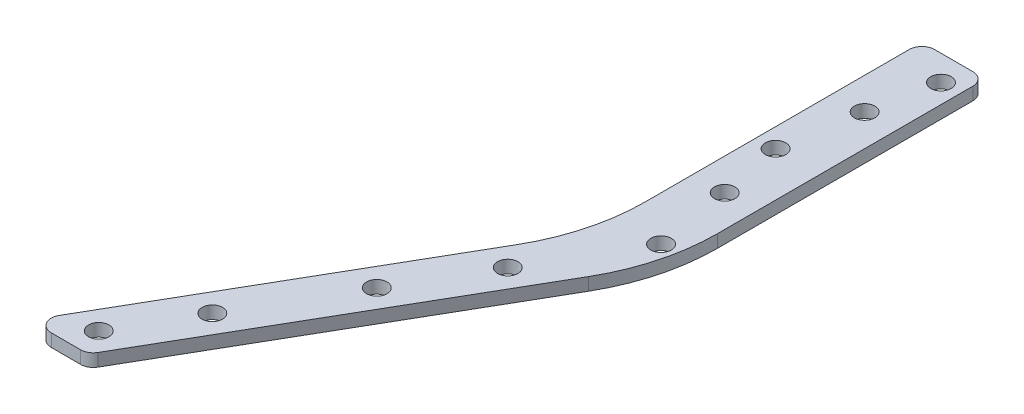
SolidWorks part; units mm, degrees
material "6061-T6 (SS)"
ref_plane "Front" through (0, 0, 0) normal (0, 0, 1) x (1, 0, 0)
ref_plane "Top" through (0, 0, 0) normal (0, 1, 0) x (1, 0, 0)
ref_plane "Right" through (0, 0, 0) normal (1, 0, 0) x (0, 0, -1)
sketch "Sketch1" plane through (0, 0, 0) normal (0, 1, 0) x (1, 0, 0)
  line L0 (0, -82.55) -> (-51.3264, -171.45)
  line L1 (0, 0) -> (15.875, 0)
  line L2 (0, 0) -> (0, -82.55)
  line L4 (15.875, 0) -> (15.875, -80.4537)
  line L7 (-51.3264, -171.45) -> (-36.6617, -171.45)
  line L8 (-36.6617, -171.45) -> (15.875, -80.4537)
  dimension "D1" = 15.875
  dimension "D2" = 82.55
  dimension "D3" = 12.7
  dimension "D4" = 171.45
  dimension "D5" = 150
base flange "Base-Flange1" sketch "Sketch1" thickness 3.175 reverse thickness direction no parameters "D1"=3.175
sketch "Sketch6" plane through (0, 0, 0) normal (0, 1, 0) x (1, 0, 0)
  line L1 (11.1125, -6.35) -> (4.7625, -41.275) construction
  line L3 (4.7625, -41.275) -> (11.1125, -76.2) construction
  line L4 (15.875, -80.4537) -> (15.875, 0) construction
  line L5 (0, 0) -> (0, -82.55) construction
  line L6 (15.875, 0) -> (0, 0) construction
  line L7 (6.1452, -84.6063) -> (-43.9941, -171.45) construction
  line L8 (0, -82.55) -> (-51.3264, -171.45) construction
  line L9 (-51.3264, -171.45) -> (-36.6617, -171.45) construction
  circle A4 centre (-40.3279, -165.1) radius 2.5527
  circle A5 centre (-14.9279, -121.1059) radius 2.5527
  circle A6 centre (11.1125, -6.35) radius 2.5527
  circle A7 centre (4.7625, -41.275) radius 2.5527
  circle A8 centre (11.1125, -76.2) radius 2.5527
  dimension "D1" = 5.1054
  dimension "D2" = 69.85
  dimension "D3" = 4.7625
  dimension "D4" = 4.7625
  dimension "D5" = 6.35
  dimension "D7" = 5.1054
  dimension "D8" = 6.35
  dimension "D9" = 50.8
  dimension "D6" = 6.35
extrude "Cut-Extrude1" cut sketch "Sketch6" against normal through all normal cut yes
fillet "Fillet1" radius 3.175 4 edges at (0, -1.5875, 0) (15.875, -1.5875, 0) (-51.3264, -1.5875, 171.45) (-36.6617, -1.5875, 171.45)
fillet "Fillet2" radius 50.8 2 edges at (0, -1.5875, 82.55) (15.875, -1.5875, 80.4537)
sketch "Sketch9" plane through (0, 0, 0) normal (0, 1, 0) x (1, 0, 0)
  line L0 (7.9375, 0) -> (7.9375, -105.5093) construction
  line L1 (12.7, 0) -> (3.175, 0) construction
  line L2 (-45.8272, -174.625) -> (6.0364, -84.7946) construction
  line L4 (-51.3264, -171.45) -> (-40.3279, -177.8) construction
  line L6 (-6.8059, -94.3382) -> (-48.5768, -166.6875) construction
  line L7 (-45.8272, -171.45) -> (-38.4948, -171.45) construction
  line L8 (-35.7452, -169.8625) -> (9.0691, -92.2419) construction
  point P0 (7.9375, -22.225)
  point P2 (7.9375, -57.15)
  point P4 (-2.9647, -100.385)
  point P6 (-29.9522, -147.1287)
  dimension "D1" = 22.225
  dimension "D2" = 34.925
  dimension "D3" = 31.75
  dimension "D4" = 85.725
hole_wizard "#10 Clearance Hole1" positions "Sketch9" profile "Sketch8" hole size "#10" standard "ANSI Inch" end condition through all
sketch "Sketch8" plane through (7.9375, 0, 22.225) normal (1, 0, 0) x (0, 0, 1)
  line L0 (0, 0) -> (0, 3.175)
  line L1 (0, 3.175) -> (2.5527, 3.175)
  line L2 (2.5527, 3.175) -> (2.5527, 0)
  line L5 (2.5527, 0) -> (0, 0)
  line L11 (0, -6.35) -> (0, 107.95) construction
  dimension "Thru Hole Dia." = 5.1054
  dimension "Thru Hole Depth" = 3.175
sketch "Bend-Lines1" [suppressed] plane through (0, 0, 0) normal (0, 1, 0) x (1, 0, 0)
sketch "Bounding-Box1" [suppressed] plane through (0, 0, 0) normal (0, 1, 0) x (1, 0, 0)
sheet metal parameters "Sheet-Metal8" thickness 3.175 parameters "D1"=3.175
flat pattern "Flat-Pattern8" [suppressed]
sketch "Bend-Lines2" plane through (0, 0, 0) normal (0, 1, 0) x (1, 0, 0)
sketch "Bounding-Box2" [suppressed] plane through (0, 0, 0) normal (0, 1, 0) x (1, 0, 0)
sheet metal parameters "Sheet-Metal9" thickness 3.175 parameters "D1"=3.175
flat pattern "Flat-Pattern8"
sketch "Bend-Lines2" plane through (0, 0, 0) normal (0, 1, 0) x (1, 0, 0)
sketch "Bounding-Box2" [suppressed] plane through (0, 0, 0) normal (0, 1, 0) x (1, 0, 0)
sheet metal parameters "Sheet-Metal10" thickness 3.175 parameters "D1"=3.175
flat pattern "Flat-Pattern8"
sketch "Bend-Lines2" plane through (0, 0, 0) normal (0, 1, 0) x (1, 0, 0)
sketch3d "Bounding-Box2" [suppressed]
  line L0 (-49.774, -170.4153, 0) -> (1.8059, 3.3702, 0) construction
  line L1 (-15.679, -180.5348, 0) -> (35.9009, -6.7493, 0) construction
  line L2 (-49.774, -170.4153, 0) -> (-15.679, -180.5348, 0) construction
  line L3 (1.8059, 3.3702, 0) -> (35.9009, -6.7493, 0) construction
